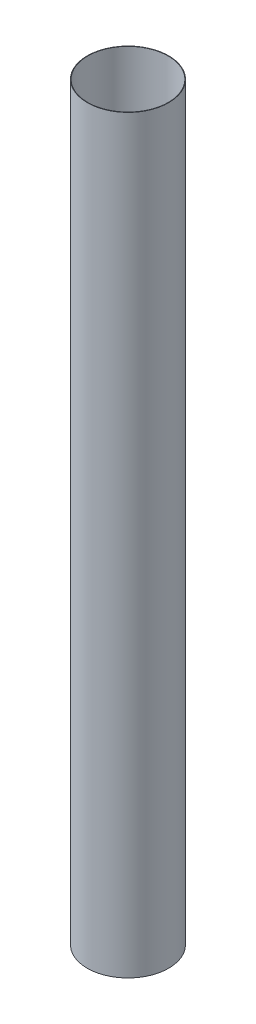
SolidWorks part; units mm, degrees
material "Ceramic Porcelain"
ref_plane "Front" through (0, 0, 0) normal (0, 0, 1) x (1, 0, 0)
ref_plane "Top" through (0, 0, 0) normal (0, 1, 0) x (1, 0, 0)
ref_plane "Right" through (0, 0, 0) normal (1, 0, 0) x (0, 0, -1)
sketch "Sketch1" plane through (0, 0, 0) normal (0, 1, 0) x (1, 0, 0)
  circle A0 centre (0, 0) radius 311.15
  circle A1 centre (0, 0) radius 314.325
  dimension "D1" = 622.3
  dimension "D2" = 628.65
extrude "Boss-Extrude1" add sketch "Sketch1" along normal blind 5791.2
